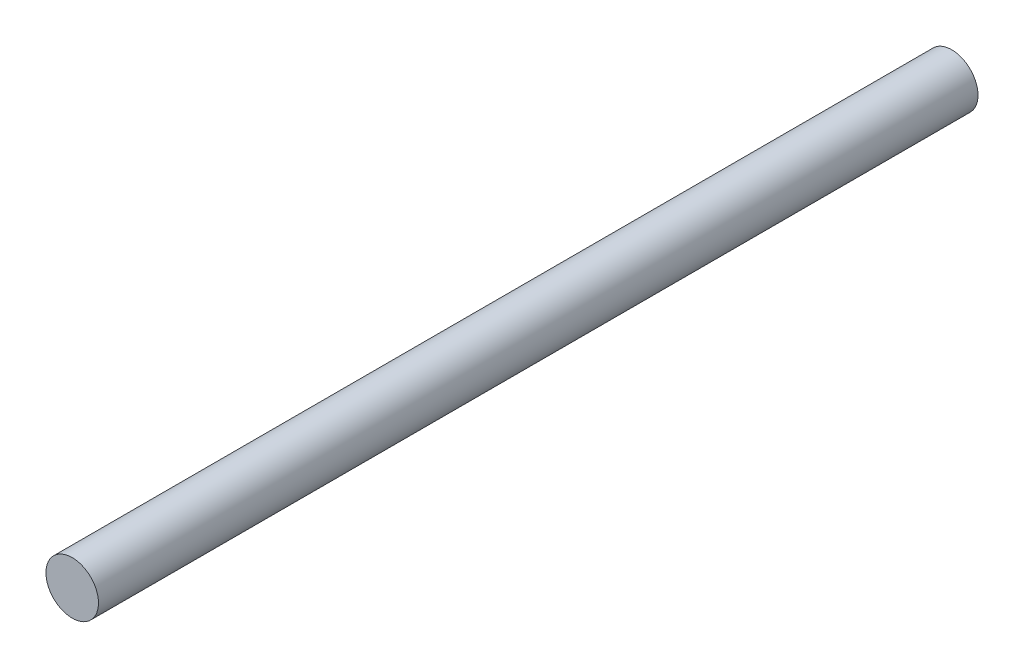
SolidWorks part; units mm, degrees
ref_plane "Front Plane" through (0, 0, 0) normal (0, 0, 1) x (1, 0, 0)
ref_plane "Top Plane" through (0, 0, 0) normal (0, 1, 0) x (1, 0, 0)
ref_plane "Right Plane" through (0, 0, 0) normal (1, 0, 0) x (0, 0, -1)
sketch "Sketch1" plane through (0, 0, 0) normal (0, 0, 1) x (1, 0, 0)
  circle A0 centre (0, 0) radius 20
  dimension "D1" = 40
extrude "Boss-Extrude1" add sketch "Sketch1" along normal mid plane 670
ref_axis "Axis1" through (0, 0, 335) along (0, 0, -1)
